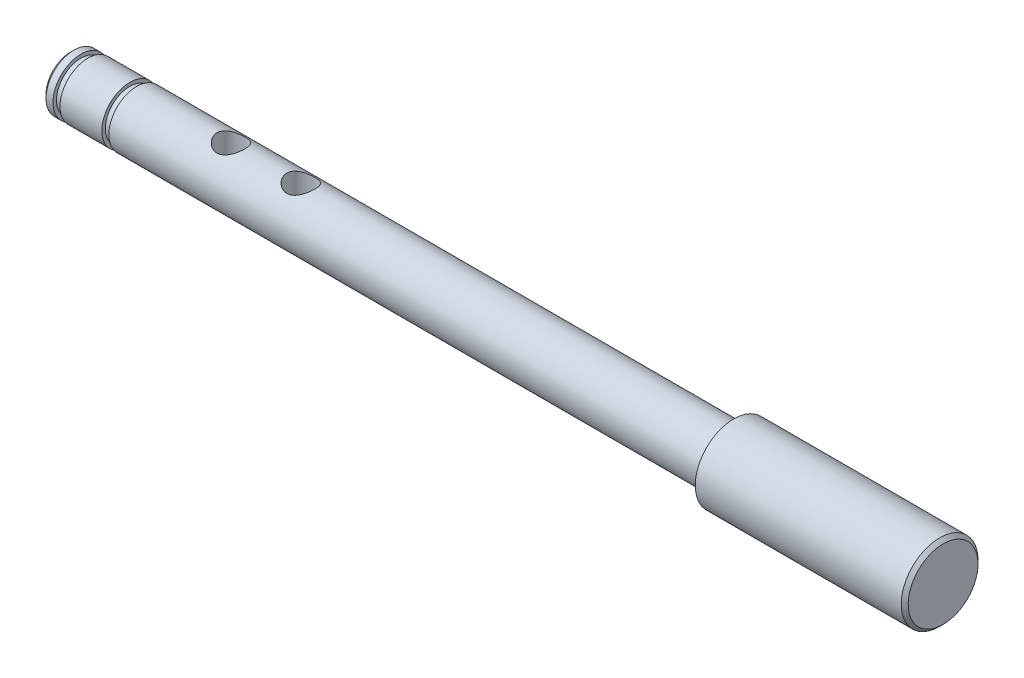
SolidWorks part; units mm, degrees
ref_plane "前视基准面" through (0, 0, 0) normal (0, 0, 1) x (1, 0, 0)
ref_plane "上视基准面" through (0, 0, 0) normal (0, 1, 0) x (1, 0, 0)
ref_plane "右视基准面" through (0, 0, 0) normal (1, 0, 0) x (0, 0, -1)
sketch "草图1" plane through (0, 0, 0) normal (0, 0, 1) x (1, 0, 0)
  line L6 (-32.9999, 0) -> (-32.9999, 3.5)
  line L7 (-32.4999, 4) -> (-32.9999, 3.5)
  line L8 (-32.4999, 4) -> (-31.4999, 4)
  line L9 (-31.4999, 3.5) -> (-30.4999, 3.5)
  line L14 (-30.4999, 4) -> (-24.4999, 4)
  line L15 (-23.4999, 4) -> (61, 4)
  line L16 (62, 5.5) -> (91.5, 5.5)
  line L17 (-24.4999, 3.5) -> (-23.4999, 3.5)
  line L20 (-32.9999, 0) -> (92, 0)
  line L23 (62, 5.5) -> (62, 5)
  line L25 (92, 5) -> (92, 0)
  line L27 (91.5, 5.5) -> (92, 5)
  line L28 (-31.4999, 3.5) -> (-31.4999, 4)
  line L30 (-30.4999, 3.5) -> (-30.4999, 4)
  line L31 (-24.4999, 3.5) -> (-24.4999, 4)
  line L32 (-23.4999, 3.5) -> (-23.4999, 4)
  arc A2 (61, 4) -> (62, 5) centre (61, 5) ccw
revolve "旋转1" add sketch "草图1" angle 360 about L20
sketch "草图2" plane through (0, 0, 0) normal (0, 1, 0) x (1, 0, 0)
  line L0 (-32.9999, 0) -> (-9.9999, 0) construction
  line L1 (-32.9999, 3.5) -> (-32.9999, -3.5) construction
  line L2 (-9.9999, 0) -> (0.0001, 0) construction
  circle A0 centre (-9.9999, 0) radius 2
  circle A1 centre (0.0001, 0) radius 2
  dimension "D1" = 4
  dimension "D2" = 4
  dimension "D3" = 10
  dimension "D4" = 23
extrude "切除-拉伸1" cut sketch "草图2" against normal blind 10 and the other way blind 10
